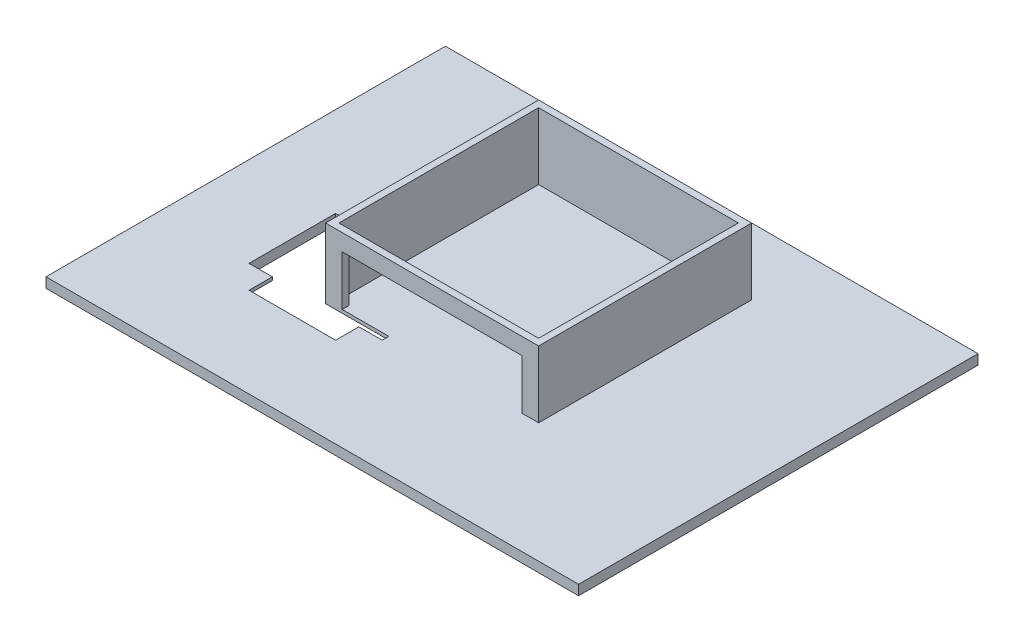
SolidWorks part; units mm, degrees
ref_plane "Front Plane" through (0, 0, 0) normal (0, 0, 1) x (1, 0, 0)
ref_plane "Top Plane" through (0, 0, 0) normal (0, 1, 0) x (1, 0, 0)
ref_plane "Right Plane" through (0, 0, 0) normal (1, 0, 0) x (0, 0, -1)
sketch "Sketch1" plane through (0, 0, 0) normal (0, 1, 0) x (1, 0, 0)
  line L1 (-80, -60) -> (80, -60)
  line L2 (-80, -60) -> (-80, 60)
  line L3 (-80, 60) -> (80, 60)
  line L4 (80, -60) -> (80, 60)
  line L5 (-80, -60) -> (80, 60) construction
  line L6 (-80, 60) -> (80, -60) construction
  point P0 (0, 0)
  dimension "D1" = 160
  dimension "D2" = 120
extrude "Boss-Extrude1" add sketch "Sketch1" along normal blind 3
sketch "Sketch2" plane through (0, 0, 0) normal (0, -1, 0) x (1, 0, 0)
  line L0 (0, 60) -> (0, 50) construction
  line L1 (-80, 60) -> (80, 60) construction
  line L2 (80, 60) -> (80, 50) construction
  line L3 (80, 60) -> (80, -60) construction
  line L4 (80, 50) -> (70, 50) construction
  line L5 (-80, 60) -> (-80, 50) construction
  line L6 (-80, -60) -> (-80, 60) construction
  line L7 (-80, 50) -> (-70, 50) construction
  line L8 (-80, 0) -> (-70, 0) construction
  line L9 (-80, -60) -> (-70, -60) construction
  line L10 (80, -60) -> (-80, -60) construction
  line L11 (-70, -60) -> (-70, -50) construction
  line L12 (80, 0) -> (70, 0) construction
  line L13 (80, -60) -> (70, -60) construction
  line L14 (70, -60) -> (70, -50) construction
  line L15 (0, -60) -> (0, -50) construction
  circle A0 centre (-70, 50) radius 3
  circle A1 centre (0, 50) radius 3
  circle A2 centre (70, 50) radius 3
  circle A3 centre (-70, 0) radius 3
  circle A4 centre (70, 0) radius 3
  circle A5 centre (-70, -50) radius 3
  circle A6 centre (0, -50) radius 3
  circle A7 centre (70, -50) radius 3
  dimension "D12" = 10
  dimension "D13" = 6
  dimension "D14" = 6
  dimension "D15" = 6
  dimension "D16" = 6
  dimension "D17" = 6
  dimension "D18" = 6
  dimension "D19" = 6
  dimension "D20" = 6
  dimension "D1" = 10
  dimension "D2" = 10
  dimension "D3" = 10
  dimension "D4" = 10
  dimension "D5" = 10
  dimension "D6" = 10
  dimension "D7" = 10
  dimension "D8" = 10
  dimension "D9" = 10
  dimension "D10" = 10
  dimension "D11" = 10
extrude "Cut-Extrude1" cut sketch "Sketch2" against normal blind 2
sketch "Sketch3" plane through (0, 0, 0) normal (0, -1, 0) x (1, 0, 0)
  line L0 (-80, 60) -> (-53, 60) construction
  line L1 (-80, 60) -> (80, 60) construction
  line L2 (-53, 60) -> (-53, 33) construction
  line L4 (-53, 33) -> (-13, 33)
  line L5 (-53, 33) -> (-53, -7)
  line L6 (-53, -7) -> (-13, -7)
  line L7 (-13, 33) -> (-13, -7)
  dimension "D1" = 27
  dimension "D2" = 27
  dimension "D3" = 40
  dimension "D4" = 40
extrude "Cut-Extrude2" cut sketch "Sketch3" against normal blind 2
sketch "Sketch4" plane through (0, 2, 0) normal (0, -1, 0) x (1, 0, 0)
  line L0 (-46, 33) -> (-20, 33)
  line L1 (-13, 33) -> (-53, 33) construction
  line L2 (-13, 33) -> (-53, 33) construction
  line L3 (-20, 33) -> (-20, 26)
  line L4 (-20, 26) -> (-13, 26)
  line L5 (-13, -7) -> (-13, 33) construction
  line L6 (-13, 26) -> (-13, 0)
  line L7 (-13, -7) -> (-13, 33) construction
  line L8 (-13, 0) -> (-20, 0)
  line L9 (-20, 0) -> (-20, -7)
  line L10 (-53, -7) -> (-13, -7) construction
  line L11 (-20, -7) -> (-46, -7)
  line L12 (-53, -7) -> (-13, -7) construction
  line L13 (-46, -7) -> (-46, 0)
  line L14 (-46, 0) -> (-53, 0)
  line L15 (-53, 33) -> (-53, -7) construction
  line L16 (-53, 0) -> (-53, 26)
  line L17 (-53, 33) -> (-53, -7) construction
  line L18 (-53, 26) -> (-46, 26)
  line L19 (-46, 26) -> (-46, 33)
  dimension "D1" = 7
  dimension "D2" = 7
  dimension "D3" = 7
  dimension "D4" = 7
  dimension "D5" = 7
  dimension "D6" = 7
  dimension "D7" = 7
  dimension "D8" = 7
extrude "Cut-Extrude3" cut sketch "Sketch4" against normal blind 1
sketch "Sketch5" plane through (0, 3, 0) normal (0, 1, 0) x (1, 0, 0)
  line L0 (0, 60) -> (0, 40) construction
  line L1 (80, 60) -> (-80, 60) construction
  line L2 (0, 40) -> (-32, 40)
  line L3 (-32, 40) -> (-32, -24)
  line L4 (-32, -24) -> (32, -24)
  line L5 (32, -24) -> (32, 40)
  line L6 (32, 40) -> (0, 40)
  dimension "D1" = 32
  dimension "D2" = 32
  dimension "D3" = 64
  dimension "D4" = 20
extrude "Boss-Extrude2" add sketch "Sketch5" along normal blind 20
sketch "Sketch6" plane through (0, 3, 0) normal (0, -1, 0) x (1, 0, 0)
  line L0 (-32, 24) -> (-13, 24)
  line L1 (-13, 24) -> (-13, 0)
  line L2 (-13, 0) -> (-20, 0)
  line L3 (-20, 0) -> (-20, -7)
  line L4 (-20, -7) -> (-32, -7)
  line L5 (-32, -7) -> (-32, 24)
extrude "Boss-Extrude3" add sketch "Sketch6" along normal blind 1
sketch "Sketch7" plane through (0, 23, 0) normal (0, 1, 0) x (1, 0, 0)
  line L0 (32, 40) -> (-32, 40) construction
  line L1 (-30, 38) -> (30, 38)
  line L2 (-30, 38) -> (-30, -22)
  line L3 (-30, -22) -> (30, -22)
  line L4 (30, 38) -> (30, -22)
  line L5 (32, -24) -> (32, 40) construction
  dimension "D1" = 2
  dimension "D2" = 2
  dimension "D3" = 60
  dimension "D4" = 60
extrude "Cut-Extrude4" cut sketch "Sketch7" against normal blind 20
sketch "Sketch8" plane through (0, 0, 24) normal (0, 0, 1) x (1, 0, 0)
  line L0 (-80, 3) -> (80, 3) construction
  line L1 (-27, 3) -> (27, 3)
  line L2 (-27, 3) -> (-27, 18)
  line L3 (-27, 18) -> (27, 18)
  line L4 (27, 3) -> (27, 18)
  line L5 (32, 23) -> (32, 3) construction
  line L6 (-32, 23) -> (-32, 2) construction
  dimension "D1" = 15
  dimension "D2" = 5
  dimension "D3" = 5
extrude "Cut-Extrude5" cut sketch "Sketch8" against normal up to next
